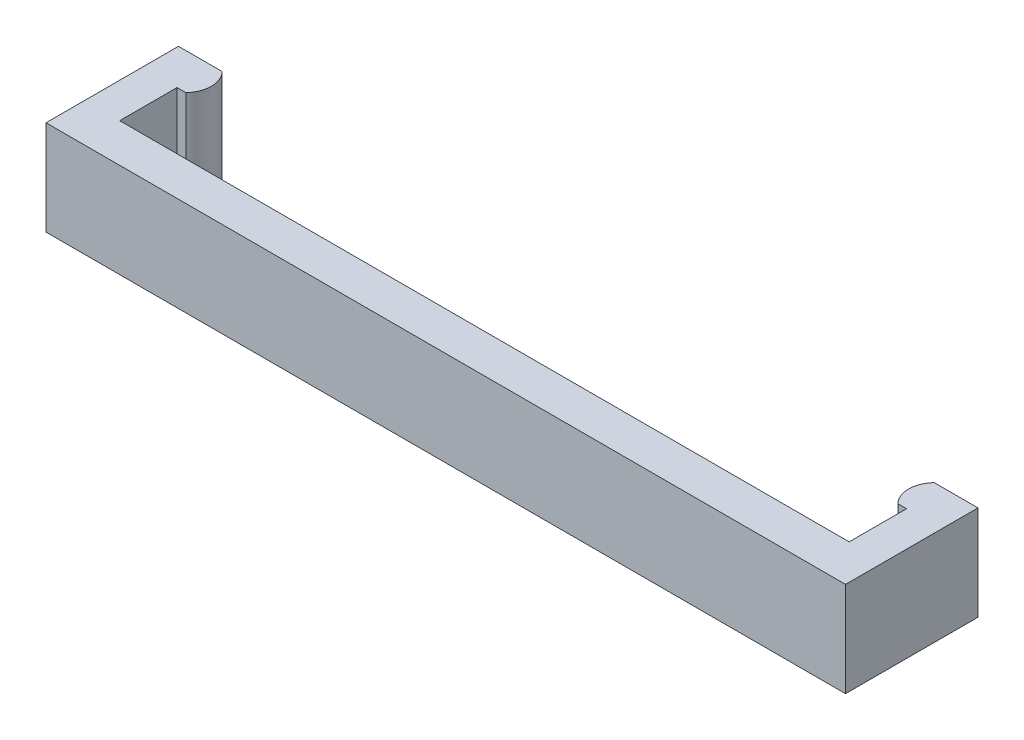
SolidWorks part; units mm, degrees
ref_plane "Front Plane" through (0, 0, 0) normal (0, 0, 1) x (1, 0, 0)
ref_plane "Top Plane" through (0, 0, 0) normal (0, 1, 0) x (1, 0, 0)
ref_plane "Right Plane" through (0, 0, 0) normal (1, 0, 0) x (0, 0, -1)
sketch "Sketch1" plane through (0, 0, 0) normal (0, -1, 0) x (1, 0, 0)
  line L0 (38.86, 36.51) -> (-11.94, 36.51) construction
  line L1 (38.86, 31.43) -> (38.86, 36.51) construction
  line L2 (37.86, 35.51) -> (37.86, 32.43) construction
  line L3 (-10.94, 35.51) -> (37.86, 35.51) construction
  line L4 (38.86, 36.51) -> (-11.94, 36.51)
  line L5 (38.86, 31.43) -> (38.86, 36.51)
  line L6 (37.86, 35.51) -> (37.86, 32.43)
  line L7 (-10.94, 35.51) -> (37.86, 35.51)
sketch "Sketch2" plane through (0, 0, 0) normal (0, -1, 0) x (1, 0, 0)
  line L0 (13.46, 38.51) -> (13.46, 36.51) construction
  line L1 (-13.94, 29.43) -> (40.86, 29.43)
  line L2 (-13.94, 29.43) -> (-13.94, 38.51)
  line L3 (-13.94, 38.51) -> (40.86, 38.51)
  line L4 (40.86, 29.43) -> (40.86, 38.51)
  line L5 (38.86, 36.51) -> (-11.94, 36.51) construction
  line L6 (40.86, 33.97) -> (38.86, 33.97) construction
  line L7 (38.86, 31.43) -> (38.86, 36.51) construction
  dimension "D1" = 2
  dimension "D2" = 2
extrude "Boss-Extrude1" add sketch "Sketch2" along normal up to surface (6.49 mm away)
sketch "Sketch3" plane through (0, 0, 0) normal (0, 1, 0) x (1, 0, 0)
  line L0 (-13.94, -29.43) -> (40.86, -29.43) construction
  line L1 (-11.54, -29.43) -> (38.46, -29.43)
  line L2 (-11.54, -29.43) -> (-11.54, -35.86)
  line L3 (-11.54, -35.86) -> (38.46, -35.86)
  line L4 (38.46, -29.43) -> (38.46, -35.86)
  line L5 (13.46, -36.51) -> (13.46, -35.86) construction
  line L6 (38.86, -36.51) -> (-11.94, -36.51) construction
  line L7 (38.86, -33.97) -> (38.46, -33.97) construction
  line L8 (38.86, -31.43) -> (38.86, -36.51) construction
  line L9 (37.86, -35.51) -> (37.86, -32.43) construction
  line L10 (-10.94, -35.51) -> (37.86, -35.51) construction
  dimension "D1" = 0.6
  dimension "D2" = 0.35
extrude "Cut-Extrude1" cut sketch "Sketch3" against normal through all
sketch "Sketch4" plane through (0, 0, 0) normal (0, 1, 0) x (1, 0, 0)
  line L0 (38.46, -29.43) -> (37.86, -29.43)
  line L1 (37.86, -31.93) -> (38.46, -31.93)
  line L2 (38.46, -35.86) -> (38.46, -29.43) construction
  line L3 (38.46, -31.93) -> (38.46, -29.43)
  line L4 (13.46, -38.51) -> (13.46, -27.5844) construction
  line L5 (40.86, -38.51) -> (-13.94, -38.51) construction
  line L6 (-10.94, -31.93) -> (-11.54, -31.93)
  line L7 (-11.54, -29.43) -> (-10.94, -29.43)
  line L8 (-11.54, -31.93) -> (-11.54, -29.43)
  line L9 (37.86, -35.51) -> (37.86, -32.43) construction
  arc A0 (37.86, -29.43) -> (37.86, -31.93) centre (39.1725, -30.68) ccw
  arc A1 (-10.94, -29.43) -> (-10.94, -31.93) centre (-12.2525, -30.68) cw
  point P17 (37.36, -30.68)
  dimension "D1" = 0.5
  dimension "D2" = 0.5
extrude "Boss-Extrude2" add sketch "Sketch4" against normal through all
